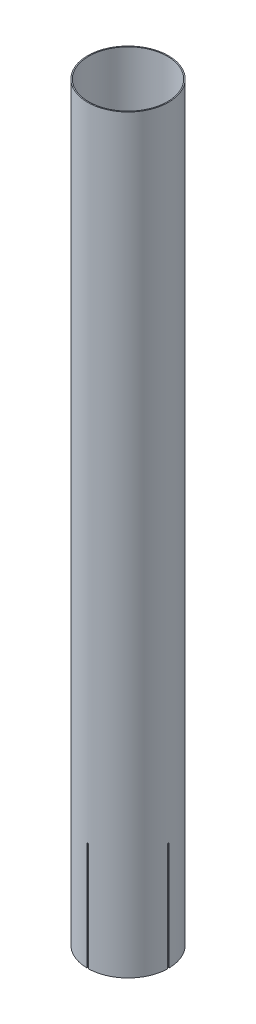
SolidWorks part; units mm, degrees
material "A-Glass Fiber"
ref_plane "Front Plane" through (0, 0, 0) normal (0, 0, 1) x (1, 0, 0)
ref_plane "Top Plane" through (0, 0, 0) normal (0, 1, 0) x (1, 0, 0)
ref_plane "Right Plane" through (0, 0, 0) normal (1, 0, 0) x (0, 0, -1)
sketch "Sketch1" plane through (0, 0, 0) normal (0, 0, 1) x (1, 0, 0)
  line L0 (78.2, 0) -> (78.2, 1450)
  line L1 (0, 0) -> (0, 2000) construction
  line L9 (76.2, 0) -> (76.2, 1450)
  line L10 (78.2, 0) -> (76.2, 0)
  line L11 (78.2, 1450) -> (76.2, 1450)
  point P7 (65, 1600)
  point P8 (-1029.1667, 1600)
  point P9 (-9.3208, 1996.3774)
  dimension "D1" = 1450
  dimension "D2" = 76.2
  dimension "D3" = 2000
  dimension "D4" = 2
revolve "Revolve1" add sketch "Sketch1" angle 360 about L1
sketch "Sketch2" plane through (0, 0, 0) normal (0, 0, 1) x (1, 0, 0)
  line L0 (-185.2, 150) -> (-185.2, 0)
  line L1 (-185.2, 0) -> (-78.2, 0)
  line L2 (-78.2, 0) -> (-78.2, 210) construction
  line L3 (-78.2, 210) -> (-185.2, 150)
  line L4 (-78.2, 0) -> (0, 0)
  line L5 (-78.2, 210) -> (0, 210)
  line L6 (0, 0) -> (0, 210)
  dimension "D1" = 210
  dimension "D2" = 150
  dimension "D3" = 107
extrude "Cut-Extrude1" cut sketch "Sketch2" against normal blind 1.5 and the other way blind 1.5
pattern_circular "CirPattern1" count 4 over 360 about axis through (0, 0, 0) along (0, -1, 0) of "Cut-Extrude1"
